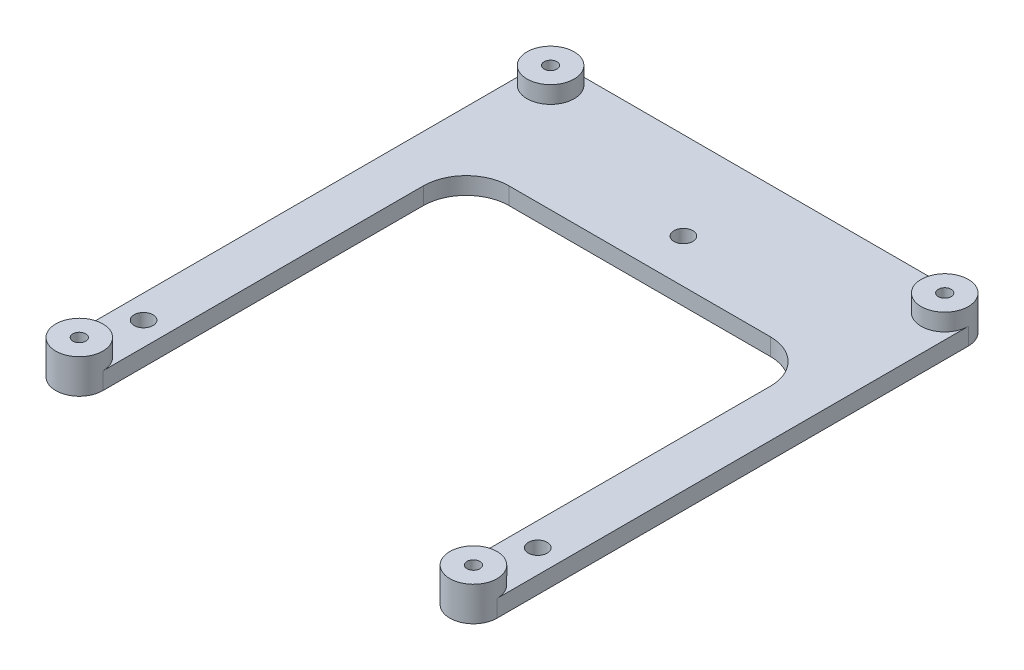
SolidWorks part; units mm, degrees
ref_plane "Front" through (0, 0, 0) normal (0, 0, 1) x (1, 0, 0)
ref_plane "Top" through (0, 0, 0) normal (0, 1, 0) x (1, 0, 0)
ref_plane "Right" through (0, 0, 0) normal (1, 0, 0) x (0, 0, -1)
sketch "Sketch1" plane through (0, 0, 0) normal (0, 1, 0) x (1, 0, 0)
  line L0 (0, 0) -> (46, 0) construction
  line L1 (23, 0) -> (23, 40) construction
  line L2 (0, 0) -> (23, 40) construction
  line L3 (23, 40) -> (46, 0) construction
  circle A0 centre (0, 0) radius 1.1
  circle A1 centre (46, 0) radius 1.1
  circle A2 centre (23, 40) radius 1.1
  dimension "D2" = 2.2
  dimension "D3" = 40
  dimension "D1" = 46
sketch "Sketch2" plane through (0, 0, 0) normal (0, 1, 0) x (1, 0, 0)
  line L0 (23, 0) -> (23, 40) construction
  line L1 (0, -7.5) -> (46, -7.5) construction
  line L2 (0, -7.5) -> (0, 47.5) construction
  line L3 (0, 47.5) -> (46, 47.5) construction
  line L4 (46, -7.5) -> (46, 47.5) construction
  line L5 (0, -7.5) -> (46, 47.5) construction
  line L6 (0, 47.5) -> (46, -7.5) construction
  line L7 (-4, 51.5) -> (50, 51.5)
  line L8 (50, -11.5) -> (50, 51.5)
  line L9 (-4, -11.5) -> (50, -11.5)
  line L10 (-4, -11.5) -> (-4, 51.5)
  circle A0 centre (46, -7.5) radius 0.75
  circle A1 centre (46, 47.5) radius 0.75
  circle A2 centre (0, 47.5) radius 0.75
  circle A3 centre (0, -7.5) radius 0.75
  point P0 (23, 20)
  dimension "D1" = 1.5
  dimension "D2" = 46
  dimension "D3" = 55
  dimension "D4" = 4
extrude "Boss-Extrude1" add sketch "Sketch2" along normal blind 2
extrude "Cut-Extrude2" cut sketch "Sketch1" against normal through all and the other way through all
sketch "Sketch3" plane through (0, 2, 0) normal (0, 1, 0) x (1, 0, 0)
  circle A0 centre (0, -7.5) radius 0.75 construction
  circle A1 centre (46, -7.5) radius 0.75 construction
  circle A2 centre (46, 47.5) radius 0.75 construction
  circle A3 centre (0, 47.5) radius 0.75 construction
  circle A4 centre (0, -7.5) radius 0.75
  circle A5 centre (46, -7.5) radius 0.75
  circle A6 centre (46, 47.5) radius 0.75
  circle A7 centre (0, 47.5) radius 0.75
  circle A8 centre (0, -7.5) radius 2.75
  circle A9 centre (46, -7.5) radius 2.75
  circle A10 centre (46, 47.5) radius 2.75
  circle A11 centre (0, 47.5) radius 2.75
  dimension "D1" = 2
extrude "Boss-Extrude2" add sketch "Sketch3" along normal blind 2
sketch "Sketch4" plane through (0, 2, 0) normal (0, 1, 0) x (1, 0, 0)
  line L0 (0, -10.25) -> (46, -10.25)
  line L1 (48.75, -7.5) -> (48.75, 47.5)
  line L2 (46, 50.25) -> (0, 50.25)
  line L3 (-2.75, 47.5) -> (-2.75, -7.5)
  arc A0 (-2.75, 47.5) -> (0, 50.25) centre (0, 47.5) cw
  circle A1 centre (0, 47.5) radius 2.75 construction
  circle A2 centre (0, 47.5) radius 2.75 construction
  arc A3 (48.75, 47.5) -> (46, 50.25) centre (46, 47.5) ccw
  circle A4 centre (46, 47.5) radius 2.75 construction
  circle A5 centre (46, 47.5) radius 2.75 construction
  arc A6 (48.75, -7.5) -> (46, -10.25) centre (46, -7.5) cw
  circle A7 centre (46, -7.5) radius 2.75 construction
  circle A8 centre (46, -7.5) radius 2.75 construction
  arc A9 (-2.75, -7.5) -> (0, -10.25) centre (0, -7.5) ccw
  circle A10 centre (0, -7.5) radius 2.75 construction
  circle A11 centre (0, -7.5) radius 2.75 construction
extrude "Cut-Extrude3" cut sketch "Sketch4" against normal through all both and the other way through all flip side to cut
sketch "Sketch5" plane through (0, 2, 0) normal (0, 1, 0) x (1, 0, 0)
  line L0 (46, -10.25) -> (0, -10.25) construction
  line L1 (2.75, -7.5) -> (2.75, 34.9)
  line L2 (2.75, 34.9) -> (43.25, 34.9)
  line L3 (43.25, 34.9) -> (43.25, -7.5)
  line L4 (23, 38.9) -> (43.25, 38.9) construction
  arc A0 (0, -10.25) -> (2.75, -7.5) centre (0, -7.5) ccw
  circle A1 centre (0, -7.5) radius 2.75 construction
  arc A2 (0, -10.25) -> (-2.75, -7.5) centre (0, -7.5) ccw construction
  arc A3 (46, -10.25) -> (43.25, -7.5) centre (46, -7.5) cw
  circle A4 centre (46, -7.5) radius 2.75 construction
  circle A5 centre (23, 40) radius 1.1 construction
  point P17 (23, 38.9)
  dimension "D1" = 4
extrude "Cut-Extrude4" cut sketch "Sketch5" against normal through all and the other way through all
fillet "Fillet1" radius 5 2 edges at (43.25, 1, -34.9) (2.75, 1, -34.9)
